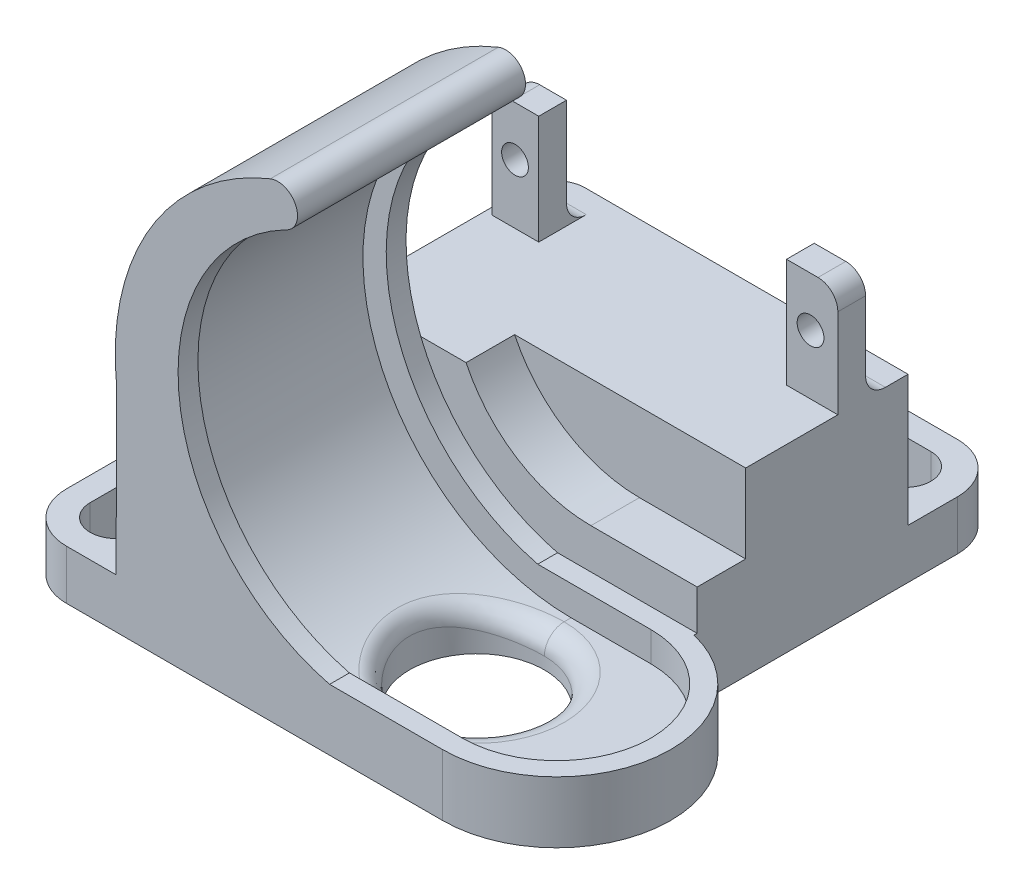
SolidWorks part; units mm, degrees
material "ABS"
ref_plane "Front Plane" through (0, 0, 0) normal (0, 0, 1) x (1, 0, 0)
ref_plane "Top Plane" through (0, 0, 0) normal (0, 1, 0) x (1, 0, 0)
ref_plane "Right Plane" through (0, 0, 0) normal (1, 0, 0) x (0, 0, -1)
sketch "Sketch1" plane through (0, 0, 0) normal (0, 1, 0) x (1, 0, 0)
  line L1 (-31.75, -12.065) -> (31.75, -12.065)
  line L2 (-31.75, -12.065) -> (-31.75, 12.065)
  line L3 (-31.75, 12.065) -> (31.75, 12.065)
  line L4 (31.75, -12.065) -> (31.75, 12.065)
  line L5 (-31.75, -12.065) -> (31.75, 12.065) construction
  line L6 (-31.75, 12.065) -> (31.75, -12.065) construction
  point P0 (0, 0)
  dimension "D1" = 24.13
  dimension "D2" = 63.5
extrude "Boss-Extrude1" add sketch "Sketch1" along normal blind 4.064
sketch "Sketch2" plane through (0, 0, 0) normal (0, 0, 1) x (1, 0, 0)
  line L0 (0, -2.2352) -> (0, 2.2352) construction
  line L1 (-31.75, 4.064) -> (31.75, 4.064) construction
  line L3 (-31.75, 4.064) -> (31.75, 4.064) construction
  line L4 (0, 4.064) -> (-26.7168, 4.064)
  line L5 (-31.571, 27.3677) -> (-26.7168, 4.064)
  arc A0 (-9.9723, 55.4695) -> (0, 4.064) centre (0, 30.734) ccw
  arc A1 (-11.8717, 60.181) -> (-31.571, 27.3677) centre (0, 30.734) ccw
  arc A2 (-9.9723, 55.4695) -> (-11.8717, 60.181) centre (-10.922, 57.8252) ccw
  dimension "D1" = 53.34
  dimension "D2" = 63.5
  dimension "D3" = 10.922
  dimension "D4" = 23.3037
  dimension "D5" = 23.8039
extrude "Boss-Extrude2" add sketch "Sketch2" along normal up to surface and the other way up to surface up to face at (0, 2.032, 12.065) other way up to face at (0, 2.032, -12.065)
sketch "Sketch4" plane through (0, 4.064, 0) normal (0, 1, 0) x (1, 0, 0)
  circle A0 centre (0, 0) radius 8.636
  dimension "D1" = 17.272
extrude "Cut-Extrude1" cut sketch "Sketch4" against normal through all and the other way blind 4.064
fillet "Fillet1" radius 2.54 2 edges at (8.636, 4.064, 0) (-8.5992, 5.4884, 0.7963)
sketch "Sketch6" plane through (0, 0, 12.065) normal (0, 0, 1) x (1, 0, 0)
  line L0 (-31.75, 4.064) -> (-26.7168, 4.064)
  line L1 (-26.7168, 4.064) -> (-25.8702, 0)
  line L2 (-25.8702, 0) -> (-31.75, 0)
  line L3 (-31.75, 4.064) -> (-31.75, 0) construction
  line L4 (-31.75, 0) -> (-31.75, 4.064)
  dimension "D1" = 4.1512
extrude "Cut-Extrude2" cut sketch "Sketch6" against normal through all
sketch "Sketch8" plane through (0, 0, 12.065) normal (0, 0, 1) x (1, 0, 0)
  line L0 (31.75, 0) -> (31.75, 7.874)
  line L1 (0, 4.064) -> (31.75, 4.064) construction
  line L2 (31.75, 0) -> (-25.8702, 0)
  line L3 (-25.8702, 0) -> (-31.571, 27.3677)
  line L4 (31.75, 7.874) -> (-23.9497, 7.874) construction
  line L5 (-4.2746, 7.874) -> (31.75, 7.874)
  arc A0 (-31.571, 27.3677) -> (-11.8717, 60.181) centre (0, 30.734) cw
  arc A1 (-11.8717, 60.181) -> (-9.9723, 55.4695) centre (-10.922, 57.8252) cw
  arc A2 (-9.9723, 55.4695) -> (-4.2746, 7.874) centre (1.9655, 32.7598) ccw
  dimension "D1" = 3.81
extrude "Boss-Extrude3" add sketch "Sketch8" along normal blind 2.54
sketch "Sketch9" plane through (0, 0, -12.065) normal (0, 0, -1) x (-1, 0, 0)
  line L0 (-31.75, 0) -> (-31.75, 7.874)
  line L1 (-31.75, 7.874) -> (4.2746, 7.874)
  line L2 (-31.75, 0) -> (25.8702, 0)
  line L3 (25.8702, 0) -> (31.571, 27.3677)
  arc A0 (31.571, 27.3677) -> (11.8717, 60.181) centre (0, 30.734) ccw
  arc A2 (9.9723, 55.4695) -> (4.2746, 7.874) centre (-1.9655, 32.7598) cw
  arc A3 (11.8717, 60.181) -> (9.9723, 55.4695) centre (10.922, 57.8252) ccw
extrude "Boss-Extrude4" add sketch "Sketch9" along normal blind 2.54
sketch "Sketch10" plane through (0, 4.064, 0) normal (0, 1, 0) x (1, 0, 0)
  line L0 (10.2183, 14.605) -> (10.2183, -14.605) construction
  line L3 (-4.2746, 14.605) -> (31.75, 14.605) construction
  line L4 (31.75, -14.605) -> (-4.2746, -14.605) construction
  line L5 (10.2183, 14.605) -> (10.2183, 12.065)
  line L6 (10.2183, -12.065) -> (10.2183, -14.605)
  arc A2 (10.2183, 14.605) -> (10.2183, -14.605) centre (10.2183, 0) cw
  arc A3 (10.2183, -12.065) -> (10.2183, 12.065) centre (10.2183, 0) ccw
extrude "Boss-Extrude5" add sketch "Sketch10" along normal blind 3.81
sketch "Sketch11" plane through (0, 7.874, 0) normal (0, 1, 0) x (1, 0, 0)
  line L0 (10.2183, 12.065) -> (10.2183, -12.065) construction
  line L1 (10.2183, 14.605) -> (10.2183, -14.605) construction
  line L2 (-4.2746, 14.605) -> (31.75, 14.605) construction
  line L3 (31.75, -14.605) -> (-4.2746, -14.605) construction
  line L4 (10.2183, 14.605) -> (31.75, 14.605)
  line L5 (31.75, 14.605) -> (31.75, -14.605)
  line L6 (31.75, -14.605) -> (10.2183, -14.605)
  arc A0 (10.2183, -14.605) -> (10.2183, 14.605) centre (10.2183, 0) ccw
extrude "Cut-Extrude3" cut sketch "Sketch11" against normal through all
sketch "Sketch12" plane through (0, 0, 0) normal (0, -1, 0) x (1, 0, 0)
  line L0 (-25.8702, -14.605) -> (-31.571, -14.605) construction
  line L1 (-31.2166, -14.605) -> (13.6144, -14.605)
  line L2 (-31.2166, -14.605) -> (-31.2166, -41.632)
  line L3 (-31.2166, -41.632) -> (13.6144, -41.632)
  line L4 (13.6144, -14.605) -> (13.6144, -41.632)
extrude "Boss-Extrude6" add sketch "Sketch12" against normal up to surface (23.114 mm away)
sketch "Sketch13" plane through (0, 0, 0) normal (0, -1, 0) x (1, 0, 0)
  line L0 (10.2183, -14.605) -> (13.6144, -14.605)
  line L1 (13.6144, -14.605) -> (13.6144, -13.3355)
  line L2 (13.6144, -13.3355) -> (10.2183, -14.605)
extrude "Boss-Extrude7" add sketch "Sketch13" against normal up to surface (7.874 mm away) up to face at (6.3056, 7.874, 0)
sketch "Sketch14" plane through (0, 0, -14.605) normal (0, 0, 1) x (1, 0, 0)
  line L0 (0, 13.0173) -> (18.6203, 13.0173)
  line L1 (18.6203, 13.0173) -> (17.7167, 30.734)
  arc A0 (17.7167, 30.734) -> (0, 13.0173) centre (0, 30.734) ccw
extrude "Cut-Extrude4" cut sketch "Sketch14" against normal up to surface (6.2198 mm away) up to face at (7.2796, 4.064, 0)
sketch "Sketch16" plane through (0, 0, -14.605) normal (0, 0, 1) x (1, 0, 0)
  line L0 (-31.2166, 23.114) -> (-30.685, 23.114)
  line L1 (-30.685, 23.114) -> (-25.8702, 0)
  line L2 (-25.8702, 0) -> (-31.2166, 0)
  line L3 (-31.2166, 0) -> (-31.2166, 23.114)
extrude "Cut-Extrude5" cut sketch "Sketch16" against normal up to surface (27.027 mm away) up to face at (-8.8011, 11.557, -41.632)
sketch "Sketch17" plane through (0, 23.114, 0) normal (0, 1, 0) x (1, 0, 0)
  line L0 (13.6144, 41.632) -> (13.6144, 20.8248) construction
  line L1 (6.6167, 32.6358) -> (13.6144, 32.6358)
  line L2 (6.6167, 32.6358) -> (6.6167, 36.1918)
  line L3 (6.6167, 36.1918) -> (13.6144, 36.1918)
  line L4 (13.6144, 32.6358) -> (13.6144, 36.1918)
  dimension "D1" = 3.556
extrude "Boss-Extrude8" add sketch "Sketch17" along normal blind 13.97
sketch "Sketch18" plane through (0, 23.114, 0) normal (0, 1, 0) x (1, 0, 0)
  line L0 (-30.685, 41.632) -> (-30.685, 14.605) construction
  line L1 (-24.2951, 32.6358) -> (-30.685, 32.6358)
  line L2 (-24.2951, 32.6358) -> (-24.2951, 36.1918)
  line L3 (-24.2951, 36.1918) -> (-30.685, 36.1918)
  line L4 (-30.685, 32.6358) -> (-30.685, 36.1918)
  dimension "D1" = 3.556
extrude "Boss-Extrude9" add sketch "Sketch18" along normal blind 13.97
sketch "Sketch19" plane through (0, 37.084, 0) normal (0, 1, 0) x (1, 0, 0)
  line L0 (-24.2951, 36.1918) -> (6.6167, 36.1918) construction
  line L1 (6.6167, 32.6358) -> (13.6144, 32.6358) construction
  line L2 (-24.7142, 39.7478) -> (7.0358, 39.7478)
  line L3 (-24.7142, 39.7478) -> (-24.7142, 32.6358)
  line L4 (-24.7142, 32.6358) -> (7.0358, 32.6358)
  line L5 (7.0358, 39.7478) -> (7.0358, 32.6358)
  line L6 (-24.7142, 39.7478) -> (7.0358, 32.6358) construction
  line L7 (-24.7142, 32.6358) -> (7.0358, 39.7478) construction
  point P4 (-8.8392, 36.1918)
  dimension "D1" = 31.75
extrude "Cut-Extrude6" cut sketch "Sketch19" against normal up to surface (13.97 mm away) up to face at (-10.4957, 23.114, -29.6026)
sketch "Sketch20" plane through (0, 0, -36.1918) normal (0, 0, -1) x (-1, 0, 0)
  circle A0 centre (27.7559, 30.734) radius 1.7145
  circle A1 centre (-10.1155, 30.734) radius 1.7145
  dimension "D1" = 3.429
  dimension "D2" = 3.429
extrude "Cut-Extrude7" cut sketch "Sketch20" against normal up to surface (3.556 mm away)
fillet "Fillet2" radius 2.54 1 edges at (10.3251, 23.114, -36.1918)
fillet "Fillet3" radius 2.54 1 edges at (-27.6996, 23.114, -36.1918)
fillet "Fillet4" radius 2.54 2 edges at (13.6144, 37.084, -34.4138) (-30.685, 37.084, -34.4138)
ref_plane "Plane1" through (-31.571, 0, 0) normal (1, 0, 0) x (0, 0, -1)
ref_plane "Plane2" through (0, 0, 0) normal (0, -1, 0) x (-1, 0, 0)
ref_plane "Plane3" through (0, 0, 14.605) normal (0, 0, 1) x (1, 0, 0)
sketch "Sketch26" plane through (0, 0, 14.605) normal (0, 0, 1) x (1, 0, 0)
  line L0 (-25.8702, 0) -> (-31.6536, 0)
  line L1 (-31.6536, 0) -> (-31.571, 27.3677)
  line L2 (-31.571, 27.3677) -> (-25.8702, 0)
extrude "Boss-Extrude10" add sketch "Sketch26" against normal blind 29.21
sketch "Sketch22" plane through (0, 0, -14.605) normal (0, 0, -1) x (-1, 0, 0)
  line L0 (30.685, 23.114) -> (31.5839, 23.114)
  line L1 (31.571, 27.3677) -> (31.6536, 0) construction
  line L2 (31.5839, 23.114) -> (31.6536, 0)
  line L3 (31.6536, 0) -> (25.8702, 0)
  line L4 (25.8702, 0) -> (30.685, 23.114)
extrude "Boss-Extrude11" add sketch "Sketch22" along normal up to surface (27.027 mm away) up to face at (-7.3316, 11.557, -41.632)
sketch "Sketch23" plane through (0, 0, 0) normal (0, -1, 0) x (1, 0, 0)
  line L0 (-38.0036, 8.255) -> (-38.0036, -42.545) construction
  line L1 (-34.7016, 8.255) -> (-34.7016, -42.545)
  line L2 (-41.3056, 8.255) -> (-41.3056, -42.545)
  line L3 (-24.8597, -47.982) -> (6.8903, -47.982) construction
  line L4 (-24.8597, -44.68) -> (6.8903, -44.68)
  line L5 (-24.8597, -51.284) -> (6.8903, -51.284)
  line L6 (-15.5546, 14.605) -> (-44.3536, 14.605)
  line L7 (-44.3536, 14.605) -> (-44.3536, -41.632)
  line L8 (-31.6536, -41.632) -> (-31.6536, 14.605) construction
  line L9 (-31.5839, -54.3319) -> (-31.5839, -54.332)
  line L10 (-31.5839, -54.332) -> (13.6144, -54.332)
  line L11 (13.6144, -54.332) -> (13.6144, -35.1035)
  line L12 (-31.6536, -41.632) -> (13.6144, -41.632) construction
  line L14 (-15.5546, 14.605) -> (-15.5546, -35.1035)
  line L15 (-15.5546, -35.1035) -> (13.6144, -35.1035)
  line L16 (-31.6536, 14.605) -> (10.2183, 14.605) construction
  arc A0 (-34.7016, 8.255) -> (-41.3056, 8.255) centre (-38.0036, 8.255) ccw
  arc A1 (-41.3056, -42.545) -> (-34.7016, -42.545) centre (-38.0036, -42.545) ccw
  arc A2 (-24.8597, -44.68) -> (-24.8597, -51.284) centre (-24.8597, -47.982) ccw
  arc A3 (6.8903, -51.284) -> (6.8903, -44.68) centre (6.8903, -47.982) ccw
  arc A5 (-44.3536, -41.632) -> (-31.5839, -54.3319) centre (-31.6536, -41.632) ccw
  point P2 (-38.0036, -17.145)
  point P7 (-8.9847, -47.982)
  point P14 (0, 0)
  point P19 (0, 0)
  point P23 (-38.0036, -16.9094)
  point P25 (-8.9847, -54.332)
  line M19 (-31.6536, 14.605) -> (-31.6536, -41.632)
  line M20 (-31.6536, -41.632) -> (13.6144, -41.632)
  line M21 (13.6144, -41.632) -> (13.6144, -14.2047)
  arc M22 (13.6144, -14.2047) -> (10.2183, 14.605) centre (10.2183, 0) ccw
  line M23 (10.2183, 14.605) -> (-31.6536, 14.605)
  circle M24 centre (0, 0) radius 8.636
  dimension "D1" = 3.302
  dimension "D2" = 3.302
  dimension "D3" = 6.35
  dimension "D4" = 50.8
  dimension "D5" = 31.75
  dimension "D6" = 6.35
  dimension "D7" = 6.35
extrude "Boss-Extrude16" add sketch "Sketch23" against normal blind 6.35 contours L7 A5 L9 L10 L11 L6 A1 L2 A0 L1 A3 L5 A2 L4 M20 M19 | M23 M19 M20 M21 M22 M24 region at (-19.6707, 0, -17.8328) region at (-32.5543, 0, -13.5135)
fillet "Fillet5" radius 6.35 2 edges at (-44.3536, 3.175, 14.605) (13.6144, 3.175, -54.332)
fillet "Fillet6" radius 3.81 1 edges at (-31.6091, 14.732, -41.632)
